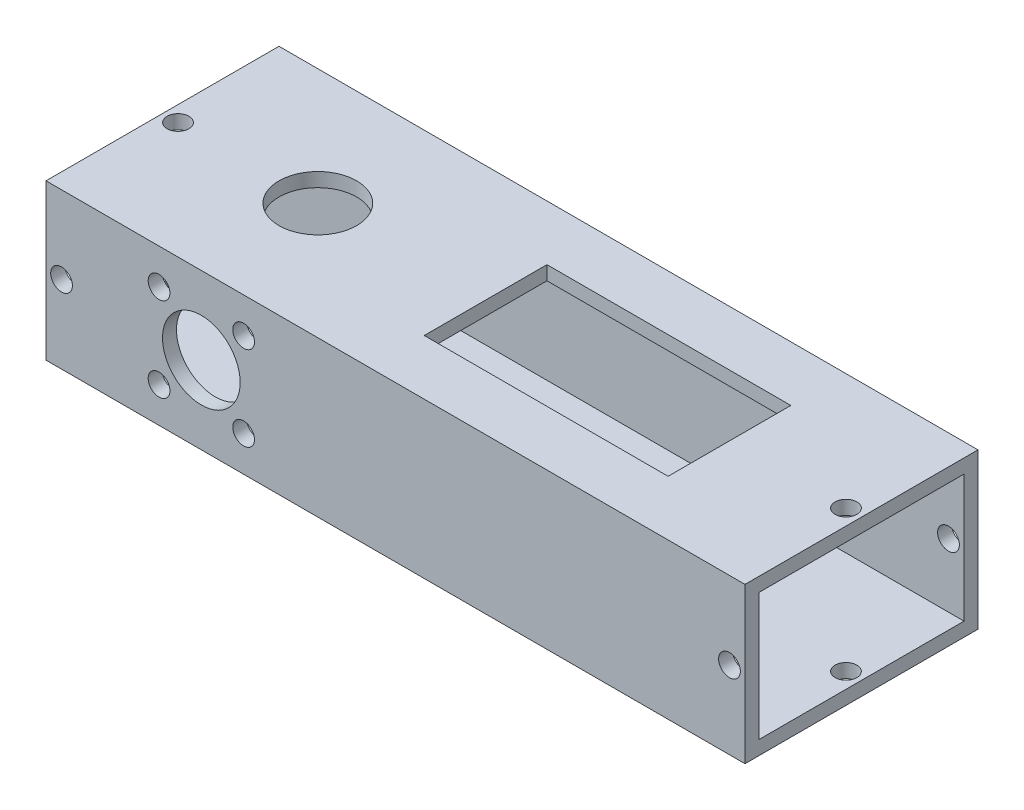
SolidWorks part; units mm, degrees
ref_plane "Front Plane" through (0, 0, 0) normal (0, 0, 1) x (1, 0, 0)
ref_plane "Top Plane" through (0, 0, 0) normal (0, 1, 0) x (1, 0, 0)
ref_plane "Right Plane" through (0, 0, 0) normal (1, 0, 0) x (0, 0, -1)
sketch "Sketch1" plane through (0, 0, 0) normal (0, 1, 0) x (1, 0, 0)
  line L1 (0, 0) -> (-114.3, 0)
  line L2 (0, 0) -> (0, -38.1)
  line L3 (0, -38.1) -> (-114.3, -38.1)
  line L4 (-114.3, 0) -> (-114.3, -38.1)
  dimension "D1" = 114.3
  dimension "D2" = 38.1
extrude "Boss-Extrude1" add sketch "Sketch1" along normal blind 25.4
sketch "Sketch2" plane through (0, 0, 0) normal (1, 0, 0) x (0, 0, -1)
  line L0 (0, 0) -> (-2.286, 0) construction
  line L1 (-38.1, 0) -> (0, 0) construction
  line L2 (-2.286, 0) -> (-2.286, 2.286) construction
  line L4 (-2.286, 2.286) -> (-35.814, 2.286)
  line L5 (-2.286, 2.286) -> (-2.286, 23.114)
  line L6 (-2.286, 23.114) -> (-35.814, 23.114)
  line L7 (-35.814, 2.286) -> (-35.814, 23.114)
  dimension "D1" = 20.828
  dimension "D2" = 33.528
extrude "Cut-Extrude1" cut sketch "Sketch2" against normal up to next
sketch "Sketch3" plane through (0, 0, 38.1) normal (0, 0, 1) x (1, 0, 0)
  line L0 (0, 0) -> (0, 12.7) construction
  line L1 (0, 25.4) -> (0, 0) construction
  line L2 (0, 12.7) -> (-2.54, 12.7) construction
  circle A0 centre (-2.54, 12.7) radius 1.778
extrude "Cut-Extrude2" cut sketch "Sketch3" against normal up to next
sketch "Sketch4" plane through (0, 0, 0) normal (0, 0, -1) x (-1, 0, 0)
  line L0 (0, 0) -> (0, 12.7) construction
  line L1 (0, 25.4) -> (0, 0) construction
  line L2 (0, 12.7) -> (2.54, 12.7) construction
  circle A0 centre (2.54, 12.7) radius 1.778
extrude "Cut-Extrude3" cut sketch "Sketch4" against normal up to next
sketch "Sketch5" plane through (0, 0, 38.1) normal (0, 0, 1) x (1, 0, 0)
  line L0 (-114.3, 0) -> (-114.3, 12.7) construction
  line L1 (-114.3, 25.4) -> (-114.3, 0) construction
  line L2 (-114.3, 12.7) -> (-111.76, 12.7) construction
  line L3 (-114.3, 12.7) -> (-88.9, 12.7) construction
  line L4 (-88.9, 12.7) -> (-81.9852, 19.6148) construction
  line L5 (-88.9, 12.7) -> (-95.8148, 5.7852) construction
  line L6 (-88.9, 12.7) -> (-81.9852, 5.7852) construction
  line L7 (-88.9, 12.7) -> (-95.8148, 19.6148) construction
  circle A0 centre (-111.76, 12.7) radius 1.778
  circle A1 centre (-88.9, 12.7) radius 6.35
  circle A2 centre (-95.8148, 19.6148) radius 1.778
  circle A3 centre (-81.9852, 19.6148) radius 1.778
  circle A4 centre (-95.8148, 5.7852) radius 1.778
  circle A5 centre (-81.9852, 5.7852) radius 1.778
  dimension "D1" = 12.7
  dimension "D2" = 3.556
extrude "Cut-Extrude4" cut sketch "Sketch5" against normal up to next
sketch "Sketch6" plane through (0, 0, 0) normal (0, 0, -1) x (-1, 0, 0)
  line L0 (114.3, 0) -> (114.3, 12.7) construction
  line L1 (114.3, 25.4) -> (114.3, 0) construction
  line L2 (114.3, 12.7) -> (111.76, 12.7) construction
  line L3 (114.3, 12.7) -> (88.9, 12.7) construction
  line L4 (88.9, 12.7) -> (81.9852, 5.7852) construction
  line L5 (88.9, 12.7) -> (95.8148, 19.6148) construction
  line L6 (88.9, 12.7) -> (95.8148, 5.7852) construction
  line L7 (88.9, 12.7) -> (81.9852, 19.6148) construction
  circle A0 centre (111.76, 12.7) radius 1.778
  circle A1 centre (88.9, 12.7) radius 6.35
  circle A2 centre (81.9852, 19.6148) radius 1.778
  circle A3 centre (95.8148, 19.6148) radius 1.778
  circle A4 centre (95.8148, 5.7852) radius 1.778
  circle A5 centre (81.9852, 5.7852) radius 1.778
  dimension "D1" = 12.7
extrude "Cut-Extrude5" cut sketch "Sketch6" against normal up to next
sketch "Sketch7" plane through (0, 25.4, 0) normal (0, 1, 0) x (1, 0, 0)
  line L0 (-114.3, -38.1) -> (-114.3, -19.05) construction
  line L1 (-114.3, 0) -> (-114.3, -38.1) construction
  line L2 (-114.3, -19.05) -> (-111.76, -19.05) construction
  line L3 (-114.3, -19.05) -> (-88.9, -19.05) construction
  line L4 (-88.9, -19.05) -> (-61.468, -19.05) construction
  line L5 (-61.468, -19.05) -> (-61.468, -9.017)
  line L6 (-61.468, -19.05) -> (-61.468, -29.083)
  line L7 (-61.468, -29.083) -> (-21.59, -29.083)
  line L8 (-61.468, -9.017) -> (-21.59, -9.017)
  line L9 (-21.59, -29.083) -> (-21.59, -9.017)
  circle A0 centre (-111.76, -19.05) radius 1.778
  circle A1 centre (-88.9, -19.05) radius 6.35
  dimension "D1" = 12.7
extrude "Cut-Extrude6" cut sketch "Sketch7" against normal up to next
sketch "Sketch8" plane through (0, 0, 0) normal (0, -1, 0) x (1, 0, 0)
  line L0 (-114.3, 38.1) -> (-114.3, 19.05) construction
  line L1 (-114.3, 0) -> (-114.3, 38.1) construction
  line L2 (-114.3, 19.05) -> (-111.76, 19.05) construction
  line L3 (-114.3, 19.05) -> (-88.9, 19.05) construction
  line L4 (-88.9, 19.05) -> (-61.468, 19.05) construction
  line L5 (-61.468, 19.05) -> (-61.468, 29.083)
  line L6 (-61.468, 19.05) -> (-61.468, 9.017)
  line L8 (-61.468, 9.017) -> (-21.59, 9.017)
  line L9 (-61.468, 29.083) -> (-21.59, 29.083)
  line L10 (-21.59, 29.083) -> (-21.59, 9.017)
  circle A0 centre (-111.76, 19.05) radius 1.778
  circle A1 centre (-88.9, 19.05) radius 6.35
  dimension "D1" = 12.7
extrude "Cut-Extrude7" cut sketch "Sketch8" against normal up to next
sketch "Sketch9" plane through (0, 25.4, 0) normal (0, 1, 0) x (1, 0, 0)
  line L0 (0, -38.1) -> (0, -19.05) construction
  line L1 (0, -38.1) -> (0, 0) construction
  line L2 (0, -19.05) -> (-2.54, -19.05) construction
  circle A0 centre (-2.54, -19.05) radius 1.778
extrude "Cut-Extrude8" cut sketch "Sketch9" against normal up to next
sketch "Sketch10" plane through (0, 0, 0) normal (0, -1, 0) x (-1, 0, 0)
  line L0 (0, -38.1) -> (0, -19.05) construction
  line L1 (0, -38.1) -> (0, 0) construction
  line L2 (0, -19.05) -> (2.54, -19.05) construction
  circle A0 centre (2.54, -19.05) radius 1.778
extrude "Cut-Extrude9" cut sketch "Sketch10" against normal up to next
sketch "Sketch11" plane through (0, 25.4, 0) normal (0, 1, 0) x (1, 0, 0)
